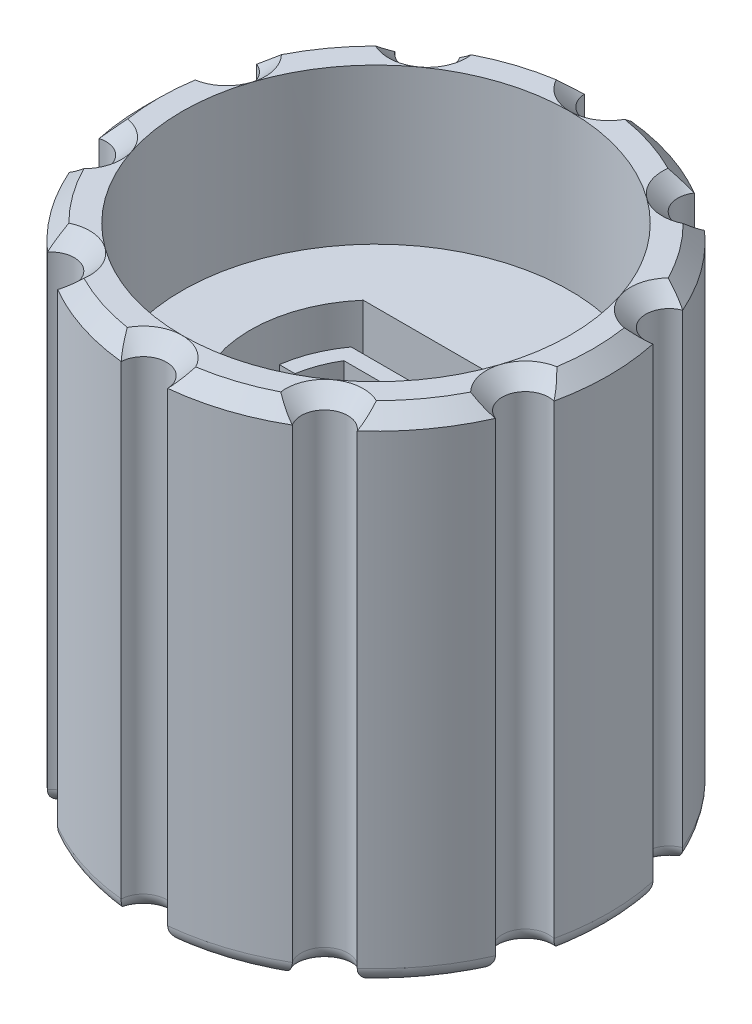
SolidWorks part; units mm, degrees
material "Custom Plastic"
ref_plane "Front Plane" through (0, 0, 0) normal (0, 0, 1) x (1, 0, 0)
ref_plane "Top Plane" through (0, 0, 0) normal (0, 1, 0) x (1, 0, 0)
ref_plane "Right Plane" through (0, 0, 0) normal (1, 0, 0) x (0, 0, -1)
sketch "Sketch1" plane through (0, 0, 0) normal (0, 1, 0) x (1, 0, 0)
  circle A0 centre (0, 0) radius 7.5
  dimension "D1" = 15
extrude "Boss-Extrude1" add sketch "Sketch1" along normal blind 16
sketch "Sketch4" plane through (0, 16, 0) normal (0, 1, 0) x (1, 0, 0)
  line L0 (0, 0) -> (0, -7.5) construction
  line L1 (0, 0) -> (4.4084, -6.0676) construction
  arc A0 (0.7491, -7.4625) -> (-0.7491, -7.4625) centre (0, -7.5) ccw
  circle A1 centre (0, 0) radius 7.5 construction
  circle A2 centre (0, 0) radius 7.5
  arc A3 (-3.7803, -6.4776) -> (-4.9924, -5.597) centre (-4.4084, -6.0676) ccw
  arc A4 (-6.8658, -3.0184) -> (-7.3287, -1.5936) centre (-7.1329, -2.3176) ccw
  arc A5 (-7.3287, 1.5936) -> (-6.8658, 3.0184) centre (-7.1329, 2.3176) ccw
  arc A6 (-4.9924, 5.597) -> (-3.7803, 6.4776) centre (-4.4084, 6.0676) ccw
  arc A7 (-0.7491, 7.4625) -> (0.7491, 7.4625) centre (0, 7.5) ccw
  arc A8 (3.7803, 6.4776) -> (4.9924, 5.597) centre (4.4084, 6.0676) ccw
  arc A9 (6.8658, 3.0184) -> (7.3287, 1.5936) centre (7.1329, 2.3176) ccw
  arc A10 (7.3287, -1.5936) -> (6.8658, -3.0184) centre (7.1329, -2.3176) ccw
  arc A11 (4.9924, -5.597) -> (3.7803, -6.4776) centre (4.4084, -6.0676) ccw
  point P37 (0, 0)
  circle M7 centre (0, 0) radius 7.5
  dimension "D1" = 1.5
  dimension "D3" = 36
  dimension "D2" = 10
extrude "Cut-Extrude3" cut sketch "Sketch4" against normal through all contours A2 A6 | A2 A7 | A2 A8 | A2 A9 | A2 A10 | A2 A11 | A0 M7 | A2 A3 | A2 A4 | A2 A5 region at (0, 16, 7.175) region at (4.2174, 16, 5.8047) region at (-4.2174, 16, 5.8047) region at (6.8239, 16, 2.2172) region at (-6.8239, 16, 2.2172) region at (-6.8239, 16, -2.2172) region at (6.8239, 16, -2.2172) region at (-4.2174, 16, -5.8047) region at (4.2174, 16, -5.8047) region at (0, 16, -7.175)
chamfer "Chamfer1" distance 0.5 angle 45 20 edges at (-3.9676, 16, 5.4609) (-6.0676, 16, 4.4084) (-6.4196, 16, 2.0859) (-7.5, 16, 0) (-6.4196, 16, -2.0859) (-6.0676, 16, -4.4084) (-3.9676, 16, -5.4609) (-2.3176, 16, -7.1329) (0, 16, -6.75) (2.3176, 16, -7.1329) (3.9676, 16, -5.4609) (6.0676, 16, -4.4084) (6.4196, 16, -2.0859) (7.5, 16, 0) (6.4196, 16, 2.0859) (6.0676, 16, 4.4084) (3.9676, 16, 5.4609) (2.3176, 16, 7.1329) (0, 16, 6.75) (-2.3176, 16, 7.1329)
fillet "Fillet1" radius 0.5 20 edges at (-3.9676, 0, 5.4609) (-2.3176, 0, 7.1329) (0, 0, 6.75) (2.3176, 0, 7.1329) (3.9676, 0, 5.4609) (6.0676, 0, 4.4084) (6.4196, 0, 2.0859) (7.5, 0, 0) (6.4196, 0, -2.0859) (6.0676, 0, -4.4084) (3.9676, 0, -5.4609) (2.3176, 0, -7.1329) (0, 0, -6.75) (-2.3176, 0, -7.1329) (-3.9676, 0, -5.4609) (-6.0676, 0, -4.4084) (-6.4196, 0, -2.0859) (-7.5, 0, 0) (-6.4196, 0, 2.0859) (-6.0676, 0, 4.4084)
sketch "Sketch5" plane through (0, 16, 0) normal (0, 1, 0) x (1, 0, 0)
  line L1 (-3.0627, 2.65) -> (3.0627, 2.65)
  arc A1 (-3.0627, 2.65) -> (3.0627, 2.65) centre (0, 0) ccw
  point P8 (0, -4.05)
  dimension "D1" = 8.1
  dimension "D2" = 6.7
extrude "Cut-Extrude4" cut sketch "Sketch5" against normal blind 14
sketch "Sketch6" plane through (0, 2, 0) normal (0, 1, 0) x (1, 0, 0)
  line L0 (2.9496, 2.15) -> (-2.9496, 2.15)
  line L3 (2.6833, 1.65) -> (-2.6833, 1.65)
  line L4 (-3.6156, 0.5) -> (-3.1101, 0.5)
  line L5 (-3.65, 0) -> (-3.15, 0)
  line L6 (-4.05, 0) -> (4.05, 0) construction
  line L8 (3.1101, 0.5) -> (3.6156, 0.5)
  line L9 (-4.05, 0.5) -> (4.05, 0.5) construction
  line L10 (3.15, 0) -> (3.65, 0)
  arc A0 (-2.9496, 2.15) -> (-3.6156, 0.5) centre (0, 0) ccw
  arc A3 (-2.6833, 1.65) -> (-3.1101, 0.5) centre (0, 0) ccw
  arc A6 (3.6156, 0.5) -> (2.9496, 2.15) centre (0, 0) ccw
  arc A7 (-2.9496, 2.15) -> (2.9496, 2.15) centre (0, 0) ccw construction
  arc A8 (3.1101, 0.5) -> (2.6833, 1.65) centre (0, 0) ccw
  arc A9 (-2.6833, 1.65) -> (2.6833, 1.65) centre (0, 0) ccw construction
  arc A10 (-3.15, 0) -> (3.15, 0) centre (0, 0) ccw
  arc A11 (-3.65, 0) -> (3.65, 0) centre (0, 0) ccw
  dimension "D1" = 3.65
  dimension "D2" = 3.15
  dimension "D5" = 2.15
  dimension "D6" = 0.5
  dimension "D3" = 0.5
  dimension "D4" = 0.5
extrude "Boss-Extrude2" add sketch "Sketch6" along normal blind 8
sketch "Sketch7" plane through (0, 16, 0) normal (0, 1, 0) x (1, 0, 0)
  line L0 (3.0627, 2.65) -> (-3.0627, 2.65) construction
  line L1 (3.0627, 2.65) -> (-3.0627, 2.65)
  circle A0 centre (0, 0) radius 6.25
  arc A1 (-3.0627, 2.65) -> (3.0627, 2.65) centre (0, 0) ccw construction
  arc A2 (-3.0627, 2.65) -> (3.0627, 2.65) centre (0, 0) ccw
  dimension "D1" = 12.5
extrude "Cut-Extrude5" cut sketch "Sketch7" against normal blind 5
